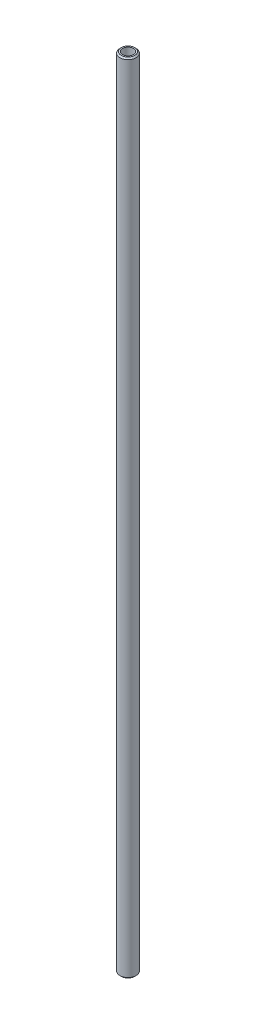
SolidWorks part; units mm, degrees
ref_plane "Plan de face" through (0, 0, 0) normal (0, 0, 1) x (1, 0, 0)
ref_plane "Plan de dessus" through (0, 0, 0) normal (0, 1, 0) x (1, 0, 0)
ref_plane "Plan de droite" through (0, 0, 0) normal (1, 0, 0) x (0, 0, -1)
sketch "Esquisse2" plane through (0, 0, 0) normal (0, 1, 0) x (1, 0, 0)
  line L0 (2002.8244, -358.3616) -> (2020.3067, -385.7591) construction
  circle A0 centre (2011.5655, -372.0603) radius 3
  circle A1 centre (2011.5655, -372.0603) radius 2
  dimension "D1" = 6
  dimension "D2" = 4
extrude "Boss.-Extru.1" add sketch "Esquisse2" along normal blind 295
chamfer "Chanfrein1" distance 0.5 angle 45 2 edges at (2011.5655, 295, 375.0603) (2011.5655, 0, 375.0603)
